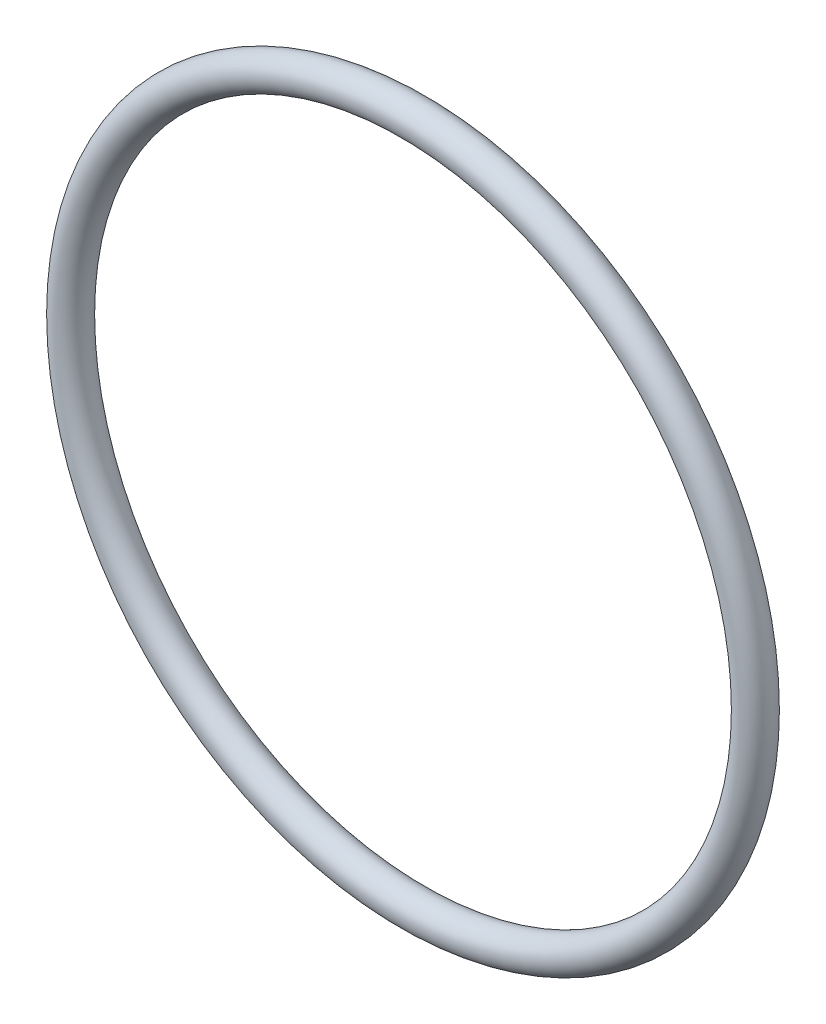
SolidWorks part; units mm, degrees
ref_plane "Front Plane" through (0, 0, 0) normal (0, 0, 1) x (1, 0, 0)
ref_plane "Top Plane" through (0, 0, 0) normal (0, 1, 0) x (1, 0, 0)
ref_plane "Right Plane" through (0, 0, 0) normal (1, 0, 0) x (0, 0, -1)
sketch "Sketch2" plane through (0, 0, 0) normal (0, 0, 1) x (1, 0, 0)
  circle A0 centre (1008, 0) radius 1008
  dimension "D1" = 2016
sketch "Sketch3" plane through (0, 0, 0) normal (0, 1, 0) x (1, 0, 0)
  circle A0 centre (0, 0) radius 50
  circle A1 centre (0, 0) radius 35
  dimension "D1" = 100
  dimension "D2" = 15
sweep "Sweep1" add profiles "Sketch3" path "Sketch2"
equation "\"hatchHoleDiameter\"=600mm"
equation "\"hullThickness\"=177.1mm"
equation "\"gasketHullInterconnectWidth\"=100mm"
equation "\"collarThickness\"=20mm"
equation "\"hatchTunnelLength\"=200mm"
equation "\"oRingDiameter\"=2mm"
equation "\"boltPatternRadiusInterconnect\"=500mm"
equation "\"interconnectBoltDiameter\"=30mm"
equation "\"hatchShaftDiameter\"=20mm"
equation "\"hatchMinima\"=39.9mm"
equation "\"hullDiameter\"=2240mm"
equation "\"hatchMaxima\"=180mm"
equation "\"bushingFlatHatch\"=15mm"
equation "\"hingePivotDiameter\"=20mm"
equation "\"handleWidth\"=250mm"
equation "\"handleHeight\"=160mm"
equation "\"handleThickness\"=25mm"
equation "\"FrameLength\"=2600mm"
equation "\"FrameMidLength\"=1800mm"
equation "\"TubeOD\"=100mm"
equation "\"FrameBackFlat\"=500mm"
equation "\"TubeWall\"=15.0001mm"
equation "\"TopMemberAngle\"=140deg"
equation "\"FrameHight\"=2500mm"
equation "\"D1@Sketch2\"=\"hullDiameter\" * .9"
equation "\"D1@Sketch3\"=\"TubeOD\""
